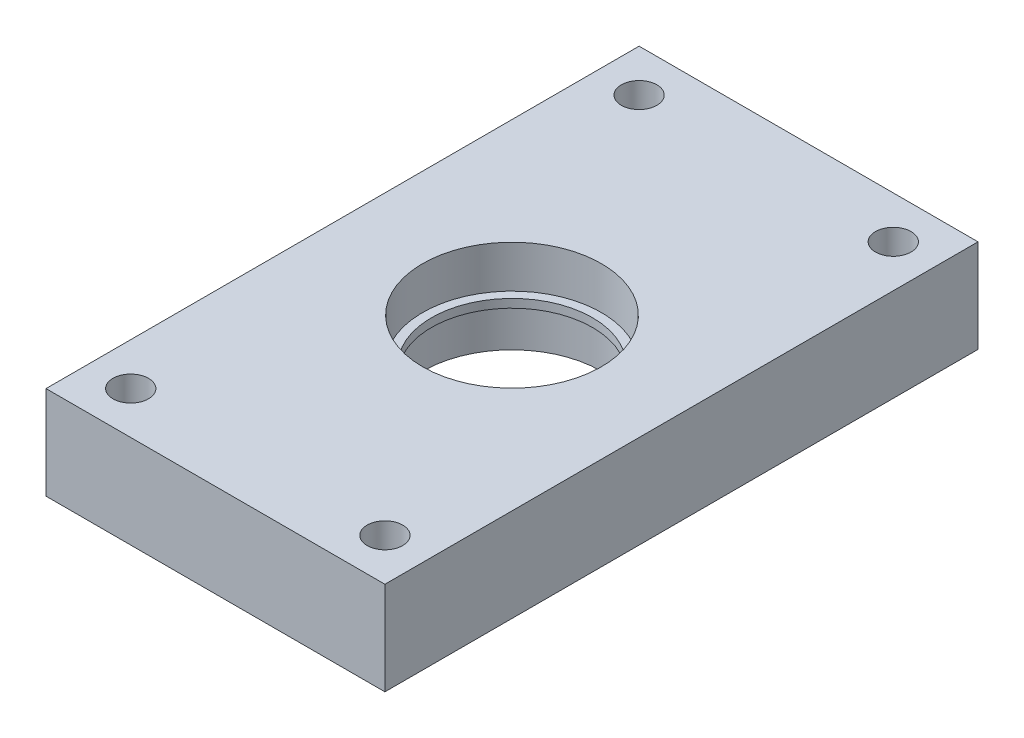
SolidWorks part; units mm, degrees
ref_plane "前视基准面" through (0, 0, 0) normal (0, 0, 1) x (1, 0, 0)
ref_plane "上视基准面" through (0, 0, 0) normal (0, 1, 0) x (1, 0, 0)
ref_plane "右视基准面" through (0, 0, 0) normal (1, 0, 0) x (0, 0, -1)
sketch "草图1" plane through (0, 0, 0) normal (0, 1, 0) x (1, 0, 0)
  line L0 (0, 0) -> (0, -58.7848) construction
  line L1 (-20, 35) -> (20, 35)
  line L2 (-20, 35) -> (-20, -35)
  line L3 (-20, -35) -> (20, -35)
  line L4 (20, 35) -> (20, -35)
  line L5 (-20, 35) -> (20, -35) construction
  line L6 (-20, -35) -> (20, 35) construction
  line L7 (0, 0) -> (35.3627, 0) construction
  line L8 (-15, -58.7848) -> (-15, 35) construction
  circle A0 centre (-15, -30) radius 2.1
  circle A1 centre (15, -30) radius 2.1
  circle A2 centre (15, 30) radius 2.1
  circle A3 centre (-15, 30) radius 2.1
  point P0 (0, 0)
  dimension "D5" = 4.2
  dimension "D1" = 70
  dimension "D2" = 40
  dimension "D3" = 5
  dimension "D4" = 5
  dimension "D6" = 60
  dimension "D7" = 30
extrude "凸台-拉伸1" add sketch "草图1" along normal blind 11
sketch "草图2" plane through (0, 11, 0) normal (0, 1, 0) x (1, 0, 0)
  circle A0 centre (0, 0) radius 9.5
  dimension "D1" = 19
extrude "切除-拉伸1" cut sketch "草图2" against normal blind 11
sketch "草图3" plane through (0, 11, 0) normal (0, 1, 0) x (1, 0, 0)
  circle A0 centre (0, 0) radius 10.55
  dimension "D1" = 21.1
extrude "切除-拉伸2" cut sketch "草图3" against normal blind 5
sketch "草图4" plane through (0, 0, 0) normal (0, -1, 0) x (1, 0, 0)
  circle A0 centre (0, 0) radius 10.55
  dimension "D1" = 21.1
extrude "切除-拉伸3" cut sketch "草图4" against normal blind 5
